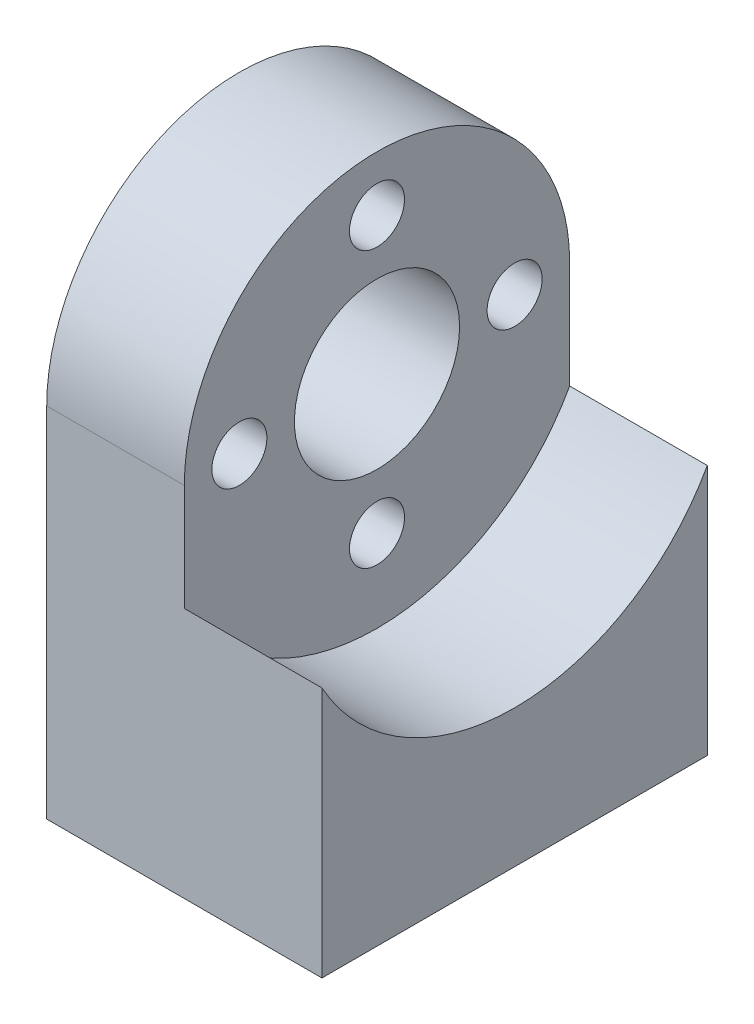
SolidWorks part; units mm, degrees
ref_plane "Front Plane" through (0, 0, 0) normal (0, 0, 1) x (1, 0, 0)
ref_plane "Top Plane" through (0, 0, 0) normal (0, 1, 0) x (1, 0, 0)
ref_plane "Right Plane" through (0, 0, 0) normal (1, 0, 0) x (0, 0, -1)
sketch "Sketch1" plane through (0, 0, 0) normal (1, 0, 0) x (0, 0, -1)
  line L0 (0, 13) -> (0, 0)
  line L1 (0, 0) -> (14, 0)
  line L2 (14, 0) -> (14, 13)
  arc A0 (0, 13) -> (14, 13) centre (7, 13) cw
  circle A1 centre (7, 13) radius 3
  circle A2 centre (12, 13) radius 1
  dimension "D2" = 6
  dimension "D4" = 2
  dimension "D1" = 14
  dimension "D3" = 5
  dimension "D5" = 13
extrude "Boss-Extrude1" add sketch "Sketch1" along normal blind 10
sketch "Sketch2" plane through (10, 0, 0) normal (1, 0, 0) x (0, 0, -1)
  circle A0 centre (7, 13) radius 8
  dimension "D1" = 16
extrude "Cut-Extrude1" cut sketch "Sketch2" against normal blind 5
pattern_circular "CirPattern1" count 4 over 360 about axis through (5, 13, -7) along (1, 0, 0) of face at (0, 13, -13)
hole_wizard "Tap Drill for M3x0.5 Tap1" positions "Sketch4" profile "Sketch3" hole size "M3x0.5" standard "ANSI Metric"
sketch "Sketch4" plane through (0, 0, 0) normal (0, -1, 0) x (-1, 0, 0)
  line L2 (-10, 0) -> (0, 0) construction
  line L3 (-10, 14) -> (0, 14) construction
  line L4 (0, 0) -> (0, 14) construction
  point P0 (-3, 11)
  point P2 (-7, 3)
  dimension "D1" = 7
  dimension "D2" = 3
  dimension "D3" = 3
  dimension "D4" = 3
sketch "Sketch3" plane through (3, 0, -11) normal (1, 0, 0) x (0, 0, -1)
  line L0 (0, 0) -> (0, 4.7511)
  line L1 (0, 4.7511) -> (1.25, 4)
  line L2 (1.25, 4) -> (1.25, 0)
  line L5 (1.25, 0) -> (0, 0)
  line L10 (0, 4.7511) -> (-1.25, 4) construction
  line L11 (0, -6.35) -> (0, 107.95) construction
  dimension "Hole Dia." = 2.5
  dimension "Hole Depth" = 4
  dimension "Drill Angle" = 118
sketch "Sketch5" plane through (0, 0, 0) normal (0, -1, 0) x (1, 0, 0)
  line L1 (7, -11) -> (3, -11) construction
  line L2 (7, -11) -> (7, -3) construction
  line L3 (7, -3) -> (3, -3) construction
  line L4 (3, -11) -> (3, -3) construction
  circle A0 centre (3, -3) radius 1
  circle A1 centre (7, -11) radius 1
  dimension "D1" = 2
extrude "Cut-Extrude2" cut sketch "Sketch5" against normal blind 4
chamfer "Chamfer1" distance 1 angle 45 4 edges at (0, 7, -7) (0, 13, -13) (0, 13, -1) (0, 19, -7)
